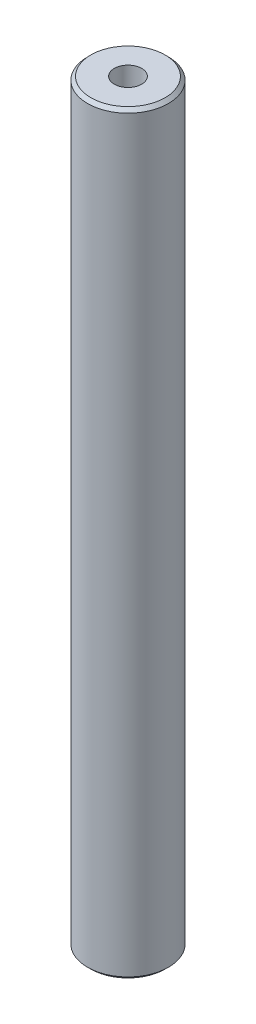
SolidWorks part; units mm, degrees
ref_plane "Front Plane" through (0, 0, 0) normal (0, 0, 1) x (1, 0, 0)
ref_plane "Top Plane" through (0, 0, 0) normal (0, 1, 0) x (1, 0, 0)
ref_plane "Right Plane" through (0, 0, 0) normal (1, 0, 0) x (0, 0, -1)
sketch "Sketch1" plane through (0, 0, 0) normal (0, 1, 0) x (1, 0, 0)
  circle A0 centre (0, 0) radius 25
  dimension "SHAFT_OD" = 50
extrude "Boss-Extrude1" add sketch "Sketch1" along normal blind 466.8548
sketch "Sketch2" plane through (0, 0, 0) normal (0, 1, 0) x (1, 0, 0)
  circle A0 centre (0, 0) radius 8.4826
  dimension "BORE_D" = 16.9652
extrude "Cut-Extrude1" cut sketch "Sketch2" along normal through all
chamfer "Chamfer1" distance 2.0972 angle 44.238 2 edges at (0, 466.8548, 25) (0, 0, 25) first distance on face at (0, 466.8548, 25) first distance on face at (0, 0, 8.4826)
